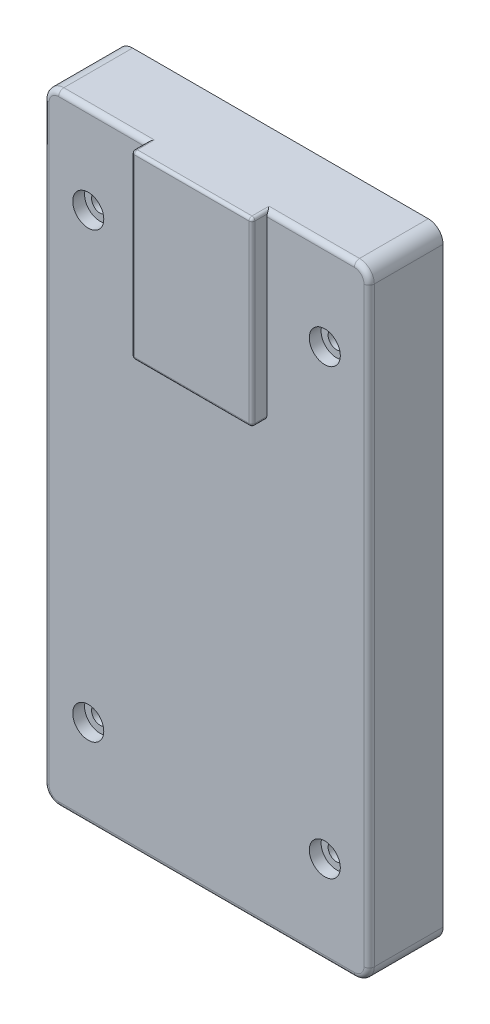
SolidWorks part; units mm, degrees
ref_plane "Front Plane" through (0, 0, 0) normal (0, 0, 1) x (1, 0, 0)
ref_plane "Top Plane" through (0, 0, 0) normal (0, 1, 0) x (1, 0, 0)
ref_plane "Right Plane" through (0, 0, 0) normal (1, 0, 0) x (0, 0, -1)
sketch "Sketch1" plane through (0, 0, 0) normal (0, 0, 1) x (1, 0, 0)
  line L1 (-22, -42) -> (22, -42)
  line L2 (-22, -42) -> (-22, 42)
  line L3 (-22, 42) -> (22, 42)
  line L4 (22, -42) -> (22, 42)
  line L5 (-22, -42) -> (22, 42) construction
  line L6 (-22, 42) -> (22, -42) construction
  point P0 (0, 0)
  dimension "D1" = 84
  dimension "D2" = 44
extrude "Boss-Extrude1" add sketch "Sketch1" along normal blind 10
sketch "Sketch2" plane through (0, 0, 10) normal (0, 0, 1) x (1, 0, 0)
  line L0 (-22, 42) -> (-8.15, 42) construction
  line L1 (22, 42) -> (-22, 42) construction
  line L3 (-8.15, 42) -> (8.15, 42)
  line L4 (-8.15, 42) -> (-8.15, 17.5)
  line L5 (-8.15, 17.5) -> (8.15, 17.5)
  line L6 (8.15, 42) -> (8.15, 17.5)
  dimension "D1" = 13.85
  dimension "D2" = 24.5
  dimension "D3" = 16.3
sketch "Sketch3" plane through (0, 0, 0) normal (0, 0, -1) x (-1, 0, 0)
  line L0 (22, -42) -> (16, -42) construction
  line L1 (22, -42) -> (-22, -42) construction
  line L2 (16, -42) -> (16, -30) construction
  line L4 (16, -30) -> (-16, -30)
  line L5 (16, -30) -> (16, 30)
  line L6 (16, 30) -> (-16, 30)
  line L7 (-16, -30) -> (-16, 30)
  dimension "D1" = 6
  dimension "D2" = 12
  dimension "D3" = 60
  dimension "D4" = 32
extrude "Boss-Extrude2" add sketch "Sketch2" along normal blind 2 contours L4 L5 L6 L3
hole_wizard "CBORE for M2 Pan Head Machine Screw1" positions "Sketch5" profile "Sketch4" counterbore size "M2" standard "ANSI Metric" end condition through all
sketch "Sketch5" plane through (0, 0, 10) normal (0, 0, 1) x (1, 0, 0)
  point P0 (16, 30)
  point P3 (-16, 30)
  point P6 (-16, -30)
  point P9 (16, -30)
sketch "Sketch4" plane through (16, 30, 10) normal (1, 0, 0) x (0, -1, 0)
  line L0 (0, 0) -> (0, 10)
  line L1 (0, 10) -> (1.15, 10)
  line L3 (1.15, 10) -> (1.15, 1.6)
  line L4 (1.15, 1.6) -> (2.1, 1.6)
  line L5 (2.1, 1.6) -> (2.1, 0)
  line L7 (2.1, 0) -> (0, 0)
  line L11 (0, -6.35) -> (0, 107.95) construction
  dimension "Thru Hole Dia." = 2.3
  dimension "Thru Hole Depth" = 10
  dimension "C'Bore Dia." = 4.2
  dimension "C'Bore Depth" = 1.6
fillet "Fillet2" radius 2 1 edges at (22, -42, 5)
fillet "Fillet3" radius 2 1 edges at (-22, -42, 5)
fillet "Fillet4" radius 2 1 edges at (-22, 42, 5)
fillet "Fillet5" radius 2 1 edges at (22, 42, 5)
fillet "Fillet6" radius 0.4 4 edges at (8.15, 29.75, 12) (0, 17.5, 12) (-8.15, 29.75, 12) (0, 42, 12)
fillet "Fillet7" radius 0.4 4 edges at (8.0328, 17.6172, 11.8828) (8.0328, 41.8828, 11.8828) (8.15, 17.5, 10.8)
fillet "Fillet8" radius 0.4 4 edges at (-8.0328, 17.6172, 11.8828) (-8.0328, 41.8828, 11.8828) (-8.15, 17.5, 10.8)
fillet "Fillet9" radius 0.7 9 edges at (21.4142, 41.4142, 10) (-21.4142, 41.4142, 10) (21.4142, -41.4142, 10) (-21.4142, -41.4142, 10) (0, -42, 10) (22, 0, 10) (-22, 0, 10)
